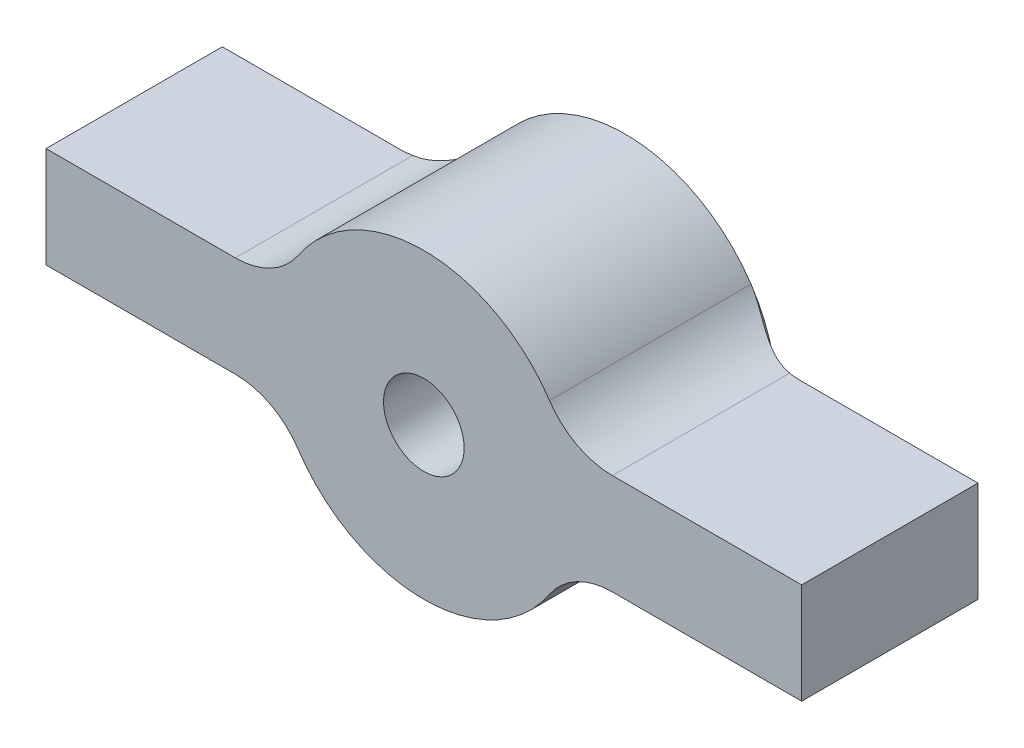
SolidWorks part; units mm, degrees
ref_plane "Спереди" through (0, 0, 0) normal (0, 0, 1) x (1, 0, 0)
ref_plane "Сверху" through (0, 0, 0) normal (0, 1, 0) x (1, 0, 0)
ref_plane "Справа" through (0, 0, 0) normal (1, 0, 0) x (0, 0, -1)
sketch "Эскиз2" plane through (0, 0, 0) normal (0, 1, 0) x (1, 0, 0)
  line L0 (0, 0) -> (0, -5.8096) construction
  line L1 (-6, 9.4) -> (-6, 3.3205) construction
  line L2 (-6, 2.1891) -> (-6, -5.8109)
  line L3 (-6, -5.8109) -> (0, -5.8109)
  line L4 (0, -5.8109) -> (0, 2.718)
  arc A0 (0, 2.718) -> (-6, 2.1891) centre (0, -31.5738) ccw
  dimension "D1" = 8
revolve "Повернуть1" add sketch "Эскиз2" angle 360 about L0
sketch "Эскиз4" plane through (0, 0, 5.8109) normal (0, 0, 1) x (1, 0, 0)
  line L1 (-15, 2) -> (15, 2)
  line L2 (-15, 2) -> (-15, -2)
  line L3 (-15, -2) -> (15, -2)
  line L4 (15, 2) -> (15, -2)
  line L5 (-15, 2) -> (15, -2) construction
  line L6 (-15, -2) -> (15, 2) construction
  point P0 (0, 0)
  dimension "D1" = 4
  dimension "D2" = 30
extrude "Бобышка-Вытянуть1" add sketch "Эскиз4" against normal blind 7
fillet "Скругление1" radius 3 6 edges at (-6, 0, -1.1891) (6, 0, -1.1891) (5.6569, -2, 2.3109) (-5.6569, -2, 2.3109) (-5.6569, 2, 2.3109) (5.6569, 2, 2.3109)
sketch "Эскиз3" plane through (0, 0, 5.8109) normal (0, 0, 1) x (1, 0, 0)
  line L1 (0, 3.2909) -> (-2.85, 1.6454)
  line L2 (-2.85, 1.6454) -> (-2.85, -1.6454)
  line L3 (-2.85, -1.6454) -> (0, -3.2909)
  line L4 (0, -3.2909) -> (2.85, -1.6454)
  line L5 (2.85, -1.6454) -> (2.85, 1.6454)
  line L6 (2.85, 1.6454) -> (0, 3.2909)
  circle A0 centre (0, 0) radius 2.85 construction
  circle A1 centre (0, 0) radius 1.6
  dimension "D1" = 5.7
extrude "Вырез-Вытянуть1" cut sketch "Эскиз3" against normal through all from offset 5.9 offset against normal yes
extrude "Вырез-Вытянуть2" cut sketch "Эскиз3<2>" against normal through all both and the other way through all contours A1 region at (0, 0, 5.8109)
sketch "Эскиз3<2>" plane through (0, 0, 5.8109) normal (0, 0, 1) x (1, 0, 0) same geometry as "Эскиз3"
